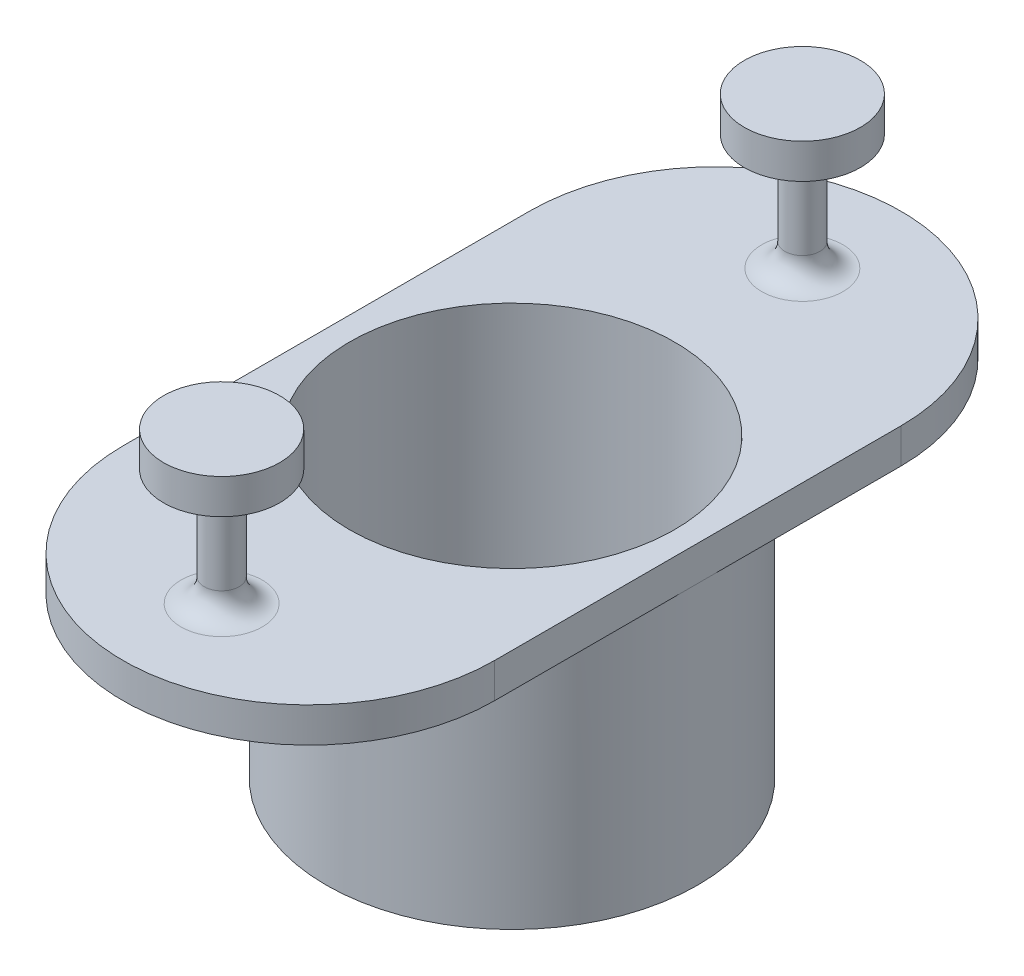
SolidWorks part; units mm, degrees
ref_plane "前视基准面" through (0, 0, 0) normal (0, 0, 1) x (1, 0, 0)
ref_plane "上视基准面" through (0, 0, 0) normal (0, 1, 0) x (1, 0, 0)
ref_plane "右视基准面" through (0, 0, 0) normal (1, 0, 0) x (0, 0, -1)
sketch "Sketch1" plane through (0, 0, 0) normal (0, 1, 0) x (1, 0, 0)
  circle A0 centre (0, 0) radius 16
  dimension "D1" = 32
extrude "Boss-Extrude1" add sketch "Sketch1" along normal blind 22.5
sketch "Sketch2" plane through (0, 22.5, 0) normal (0, 1, 0) x (1, 0, 0)
  line L0 (0, -17.5) -> (0, 17.5) construction
  line L1 (-16, -17.5) -> (-16, 17.5)
  line L2 (16, -17.5) -> (16, 17.5)
  arc A0 (-16, -17.5) -> (16, -17.5) centre (0, -17.5) ccw
  arc A1 (16, 17.5) -> (-16, 17.5) centre (0, 17.5) ccw
  circle A2 centre (0, 0) radius 16 construction
  point P2 (0, 0)
  dimension "D1" = 35
extrude "Boss-Extrude2" add sketch "Sketch2" along normal blind 3
sketch "Sketch3" plane through (0, 25.5, 0) normal (0, 1, 0) x (1, 0, 0)
  line L0 (0, -25) -> (0, 25) construction
  circle A0 centre (0, 25) radius 1.5
  circle A1 centre (0, -25) radius 1.5
  point P12 (0, 0)
  dimension "D1" = 3
  dimension "D2" = 50
extrude "Boss-Extrude3" add sketch "Sketch3" along normal blind 10
sketch "Sketch4" plane through (0, 25.5, 0) normal (0, 1, 0) x (1, 0, 0)
  circle A0 centre (0, 0) radius 14
  circle A1 centre (0, 0) radius 16 construction
  dimension "D1" = 2
extrude "Cut-Extrude1" cut sketch "Sketch4" against normal offset from surface (23.5 mm away) 2 up to face at (0, 0, 16)
sketch "Sketch5" plane through (0, 2, 0) normal (0, 1, 0) x (1, 0, 0)
  circle A0 centre (7.5, 0) radius 3 construction
  circle A1 centre (7.5, 0) radius 1.5
  circle A2 centre (-7.5, 0) radius 1.5
  point P13 (0, 0)
  dimension "D1" = 7.5
  dimension "D2" = 3
  dimension "D3" = 6
  dimension "D4" = 2
extrude "Cut-Extrude2" cut sketch "Sketch5" against normal through all
sketch "Sketch6" plane through (0, 0, 0) normal (0, -1, 0) x (1, 0, 0)
  circle A0 centre (0, 0) radius 4.3467
sketch "Sketch7" plane through (0, 35.5, 0) normal (0, 1, 0) x (1, 0, 0)
  circle A0 centre (0, 25) radius 5
  circle A1 centre (0, -25) radius 5
  dimension "D1" = 10
extrude "Boss-Extrude4" add sketch "Sketch7" along normal blind 3
fillet "Fillet1" radius 2 4 edges at (0, 35.5, -23.5) (0, 35.5, 26.5) (0, 25.5, 26.5) (0, 25.5, -23.5)
